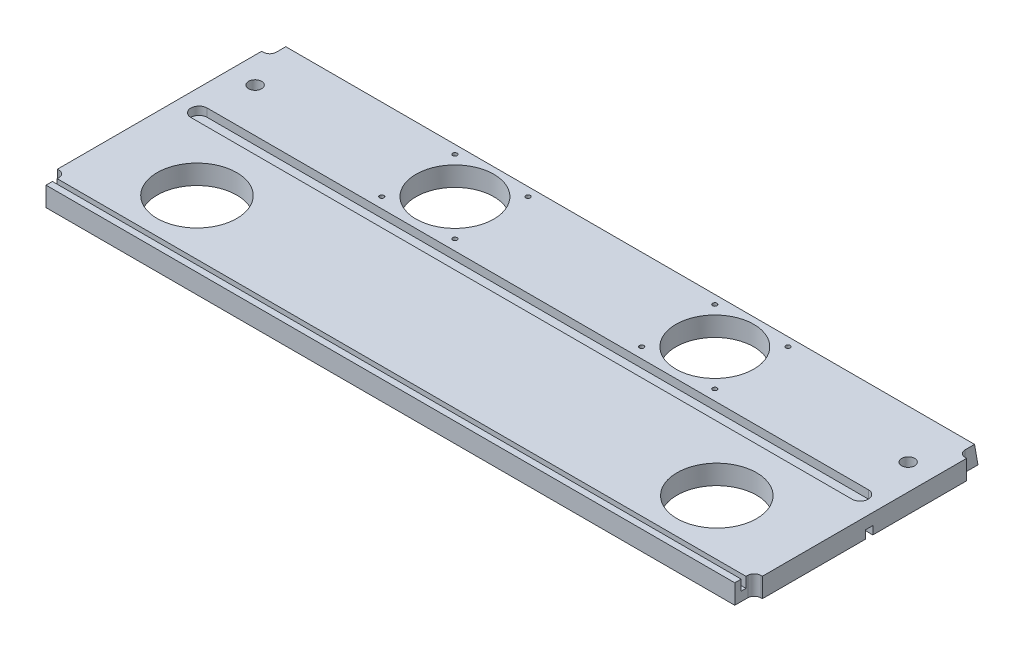
SolidWorks part; units mm, degrees
ref_plane "Front Plane" through (0, 0, 0) normal (0, 0, 1) x (1, 0, 0)
ref_plane "Top Plane" through (0, 0, 0) normal (0, 1, 0) x (1, 0, 0)
ref_plane "Right Plane" through (0, 0, 0) normal (1, 0, 0) x (0, 0, -1)
sketch "Sketch1" plane through (0, 0, 0) normal (0, 1, 0) x (1, 0, 0)
  line L0 (0, 0) -> (0, 118.8466) construction
  line L1 (336.55, 118.8466) -> (-336.55, 118.8466)
  line L2 (336.55, 118.8466) -> (336.55, -118.8466)
  line L3 (336.55, -118.8466) -> (-336.55, -118.8466)
  line L4 (-336.55, 118.8466) -> (-336.55, -118.8466)
  line L5 (336.55, 118.8466) -> (-336.55, -118.8466) construction
  line L6 (336.55, -118.8466) -> (-336.55, 118.8466) construction
  circle A0 centre (-254, -53.8734) radius 38.8937
  circle A1 centre (254, -53.8734) radius 38.8937
  point P0 (0, 0)
  dimension "D3" = 172.72
  dimension "D4" = 508
  dimension "D5" = 77.7875
  dimension "D1" = 673.1
  dimension "D2" = 237.6932
extrude "Boss-Extrude1" add sketch "Sketch1" along normal mid plane 19.05
sketch "Sketch2" plane through (0, 9.525, 0) normal (0, 1, 0) x (1, 0, 0)
  line L0 (-336.55, 118.8466) -> (-336.55, -118.8466) construction
  line L1 (-336.55, -107.89) -> (336.55, -107.89)
  line L2 (-336.55, -107.89) -> (-336.55, -112.589)
  line L3 (-336.55, -112.589) -> (336.55, -112.589)
  line L4 (336.55, -107.89) -> (336.55, -112.589)
  line L5 (336.55, -118.8466) -> (336.55, 118.8466) construction
  line L6 (-336.55, -118.8466) -> (336.55, -118.8466) construction
  dimension "D1" = 6.2576
  dimension "D2" = 4.699
extrude "Cut-Extrude1" cut sketch "Sketch2" against normal blind 10.16
sketch "Sketch3" plane through (0, 9.525, 0) normal (0, 1, 0) x (1, 0, 0)
  line L0 (-336.55, 118.8466) -> (-336.55, -107.89) construction
  line L1 (-336.55, 99.7966) -> (-344.4875, 99.7966)
  line L2 (-336.55, 99.7966) -> (-336.55, -99.7966)
  line L3 (-336.55, -99.7966) -> (-344.4875, -99.7966)
  line L4 (-344.4875, 99.7966) -> (-344.4875, -99.7966)
  line L5 (336.55, 118.8466) -> (-336.55, 118.8466) construction
  line L10 (336.55, -107.89) -> (336.55, 118.8466) construction
  line L11 (336.55, 99.7966) -> (344.4875, 99.7966)
  line L12 (336.55, 99.7966) -> (336.55, -99.7966)
  line L13 (336.55, -99.7966) -> (344.4875, -99.7966)
  line L14 (344.4875, 99.7966) -> (344.4875, -99.7966)
  line L15 (0, 0) -> (0, 51.9444) construction
  line L16 (0, 0) -> (-77.3937, 0) construction
  dimension "D1" = 19.05
  dimension "D2" = 688.975
  dimension "D3" = 7.9375
extrude "Boss-Extrude2" add sketch "Sketch3" against normal up to surface (19.05 mm away) up to face at (-254, -9.525, 92.7672)
fillet "Fillet1" radius 6.35 4 edges at (336.55, 0, -99.7966) (336.55, 0, 99.7966) (-336.55, 0, -99.7966) (-336.55, 0, 99.7966)
sketch "Sketch4" plane through (336.55, 0, 0) normal (1, 0, 0) x (0, 0, -1)
  line L0 (118.8466, -9.525) -> (115.4876, 9.525)
  line L1 (106.1466, 9.525) -> (118.8466, 9.525) construction
  line L2 (115.4876, 9.525) -> (118.8466, 9.525)
  line L3 (118.8466, 9.525) -> (118.8466, -9.525)
  dimension "D1" = 10
extrude "Cut-Extrude2" cut sketch "Sketch4" against normal through all both and the other way through all
sketch "Sketch5" plane through (0, -9.525, 0) normal (0, -1, 0) x (1, 0, 0)
  line L0 (-323.0562, -17.2022) -> (323.0562, -17.2022) construction
  line L3 (-323.0562, -9.2012) -> (323.0562, -9.2012)
  line L4 (-323.0562, -25.2032) -> (323.0562, -25.2032)
  line L5 (-336.55, 118.8466) -> (336.55, 118.8466) construction
  line L6 (0, 0) -> (0, -17.2022) construction
  arc A0 (-323.0562, -9.2012) -> (-323.0562, -25.2032) centre (-323.0562, -17.2022) ccw
  arc A1 (323.0562, -25.2032) -> (323.0562, -9.2012) centre (323.0562, -17.2022) ccw
  point P6 (0, -17.2022)
  dimension "D1" = 16.002
  dimension "D2" = 136.0488
  dimension "D3" = 646.1125
extrude "Cut-Extrude3" cut sketch "Sketch5" along normal blind 7.9375 from surface starting at face at (0, 9.525, 115.7178)
sketch "Sketch6" plane through (0, 9.525, 0) normal (0, 1, 0) x (1, 0, 0)
  line L0 (0, 0) -> (0, 115.4876) construction
  line L2 (-344.4875, 99.7966) -> (-344.4875, -99.7966) construction
  line L4 (-323.0562, 25.2032) -> (323.0562, 25.2032) construction
  circle A0 centre (-319.0875, 68.0466) radius 6.35
  circle A1 centre (319.0875, 68.0466) radius 6.35
  circle A4 centre (127, 71.2216) radius 38
  circle A5 centre (-127, 71.2216) radius 38
  circle A6 centre (162.75, 106.9716) radius 2.159
  circle A7 centre (162.75, 35.4716) radius 2.159
  circle A8 centre (91.25, 35.4716) radius 2.159
  circle A9 centre (91.25, 106.9716) radius 2.159
  circle A10 centre (127, 71.2216) radius 50.5581 construction
  circle A11 centre (-127, 71.2216) radius 50.5581 construction
  circle A12 centre (-91.25, 106.9716) radius 2.159
  circle A13 centre (-91.25, 35.4716) radius 2.159
  circle A14 centre (-162.75, 35.4716) radius 2.159
  circle A15 centre (-162.75, 106.9716) radius 2.159
  dimension "D1" = 12.7
  dimension "D2" = 25.4
  dimension "D5" = 254
  dimension "D3" = 76
  dimension "D9" = 4.318
  dimension "D4" = 46.0184
  dimension "D6" = 42.8434
  dimension "D7" = 71.5
  dimension "D8" = 71.5
extrude "Cut-Extrude4" cut sketch "Sketch6" against normal through all both and the other way through all
sketch "Sketch8" plane through (0, 0, 0) normal (1, 0, 0) x (0, 0, -1)
  line L0 (1.1534, -9.525) -> (1.1534, -1.5875)
  line L1 (1.1534, -1.5875) -> (8.1534, -1.5875)
  line L2 (8.1534, -1.5875) -> (8.1534, -9.525)
  line L3 (-99.7966, -9.525) -> (99.7966, -9.525) construction
  line L4 (1.1534, -9.525) -> (8.1534, -9.525)
  line L5 (8.1534, -9.525) -> (8.1534, -12.8771) construction
  dimension "D1" = 7
  dimension "D2" = 7.9375
  dimension "D3" = 1.1534
extrude "Cut-Extrude5" cut sketch "Sketch8" against normal through all both and the other way through all
sketch "Sketch9" plane through (0, -9.525, 0) normal (0, -1, 0) x (1, 0, 0)
  circle A0 centre (254, 53.8734) radius 53.34
  dimension "D1" = 106.68
extrude "Boss-Extrude3" [suppressed] add sketch "Sketch9" along normal blind 2.54
